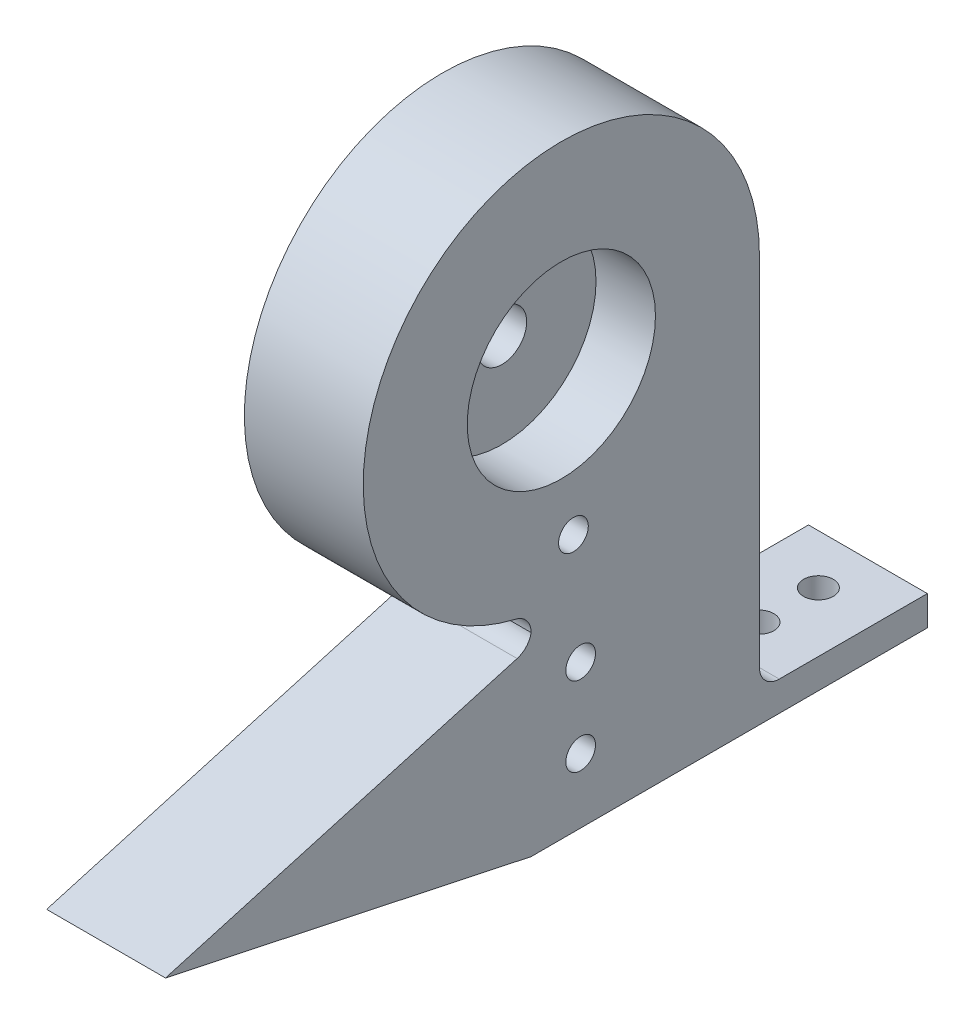
SolidWorks part; units mm, degrees
ref_plane "Front Plane" through (0, 0, 0) normal (0, 0, 1) x (1, 0, 0)
ref_plane "Top Plane" through (0, 0, 0) normal (0, 1, 0) x (1, 0, 0)
ref_plane "Right Plane" through (0, 0, 0) normal (1, 0, 0) x (0, 0, -1)
sketch "Sketch1" plane through (0, 0, 0) normal (1, 0, 0) x (0, 0, -1)
  line L11 (1.9502, -34.4799) -> (1.9502, -41) construction
  line L15 (-3.0498, -41) -> (36.9502, -41)
  line L17 (1.9502, -34.4799) -> (-3.0498, -34.4799) construction
  line L21 (20, 0) -> (20, -38)
  line L22 (20, -38) -> (36.9502, -38)
  line L23 (36.9502, -38) -> (36.9502, -41)
  line L30 (-3.0498, -19.7661) -> (-3.0498, -41)
  line L31 (-3.0498, -22.5669) -> (-3.0498, -41)
  line L32 (-3.0498, -22.5669) -> (-39.9621, -33.154)
  line L33 (-39.9621, -33.154) -> (-3.0498, -41)
  arc A2 (20, 0) -> (-3.0498, -19.7661) centre (0, 0) ccw
  circle A3 centre (0, 0) radius 9.5
  circle A9 centre (1.9502, -34.4799) radius 1.5
  circle A10 centre (1.9502, -26.4799) radius 1.5
  circle A14 centre (0, 0) radius 2.5
  circle A15 centre (1.2202, -14.9799) radius 1.5
  point P6 (1.0168, -0.1839)
  point P26 (0, 0)
  dimension "D5" = 40
  dimension "D7" = 18.4331
  dimension "D8" = 19
  dimension "D9" = 2
  dimension "D11" = 3
  dimension "D6" = 5
  dimension "D2" = 21.2339
  dimension "D3" = 40
  dimension "D4" = 38
  dimension "D10" = 5
  dimension "D12" = 28.004
  dimension "D13" = 6.5201
  dimension "D14" = 38.4006
extrude "Boss-Extrude1" add sketch "Sketch1" against normal blind 12 contours L15 L23 L22 L21 A2 L30
sketch "Sketch5" plane through (0, 0, 0) normal (1, 0, 0) x (0, 0, -1)
  line L15 (-3.0498, -41) -> (-3.0498, -58.71)
  line L16 (-3.0498, -58.71) -> (-43.0498, -58.71)
  line L17 (-43.0498, -58.71) -> (-23.9236, -51.6459)
  line L18 (-23.9236, -51.6459) -> (-23.9236, -46.3359)
  line L19 (-23.9236, -46.3359) -> (-3.0498, -30.3831)
  line L20 (-3.0498, -41) -> (-3.0498, -19.7661) construction
  line L21 (-3.0498, -30.3831) -> (-3.0498, -41)
  dimension "D2" = 17.71
  dimension "D4" = 5.31
  dimension "D5" = 40
extrude "Boss-Extrude3" [suppressed] add sketch "Sketch5" against normal up to surface (12 mm away) up to face at (-12, -25.4502, -14.3844)
extrude "Cut-Extrude1" cut sketch "Sketch1<8>" against normal up to surface (12 mm away) contours A9 | A10 | A15 up to face at (-12, -25.4502, -14.3844)
sketch "Sketch1<8>" plane through (0, 0, 0) normal (1, 0, 0) x (0, 0, -1) same geometry as "Sketch1"
extrude "Cut-Extrude2" cut sketch "Sketch1<9>" against normal blind 6 contours A3
sketch "Sketch1<9>" plane through (0, 0, 0) normal (1, 0, 0) x (0, 0, -1) same geometry as "Sketch1"
extrude "Cut-Extrude3" cut sketch "Sketch1<10>" against normal up to surface (12 mm away) contours A14 up to face at (-12, -34.4799, -3.4502)
sketch "Sketch1<10>" plane through (0, 0, 0) normal (1, 0, 0) x (0, 0, -1) same geometry as "Sketch1"
sketch "Sketch6" plane through (0, -41, 0) normal (0, -1, 0) x (1, 0, 0)
  line L0 (-6, -10.9502) -> (-6, -36.9502) construction
  line L1 (-12, -36.9502) -> (0, -36.9502) construction
  circle A0 centre (-6, -10.9502) radius 1.5
  circle A1 centre (-6, -16.9502) radius 1.5
  circle A2 centre (-6, -25.9502) radius 1.5
  circle A3 centre (-6, -31.9502) radius 1.5
  dimension "D1" = 3
extrude "Cut-Extrude4" cut sketch "Sketch6" against normal blind 10
extrude "Boss-Extrude4" add sketch "Sketch1<11>" against normal up to surface (12 mm away) contours L31 L33 L32 up to face at (-12, 0, -2.5)
sketch "Sketch1<11>" plane through (0, 0, 0) normal (1, 0, 0) x (0, 0, -1) same geometry as "Sketch1"
fillet "Fillet1" radius 2 1 edges at (-6, -38, -20)
fillet "Fillet2" radius 2 1 edges at (-6, -19.7661, 3.0498)
fillet "Fillet3" radius 2 1 edges at (-6, -22.5669, 3.0498)
